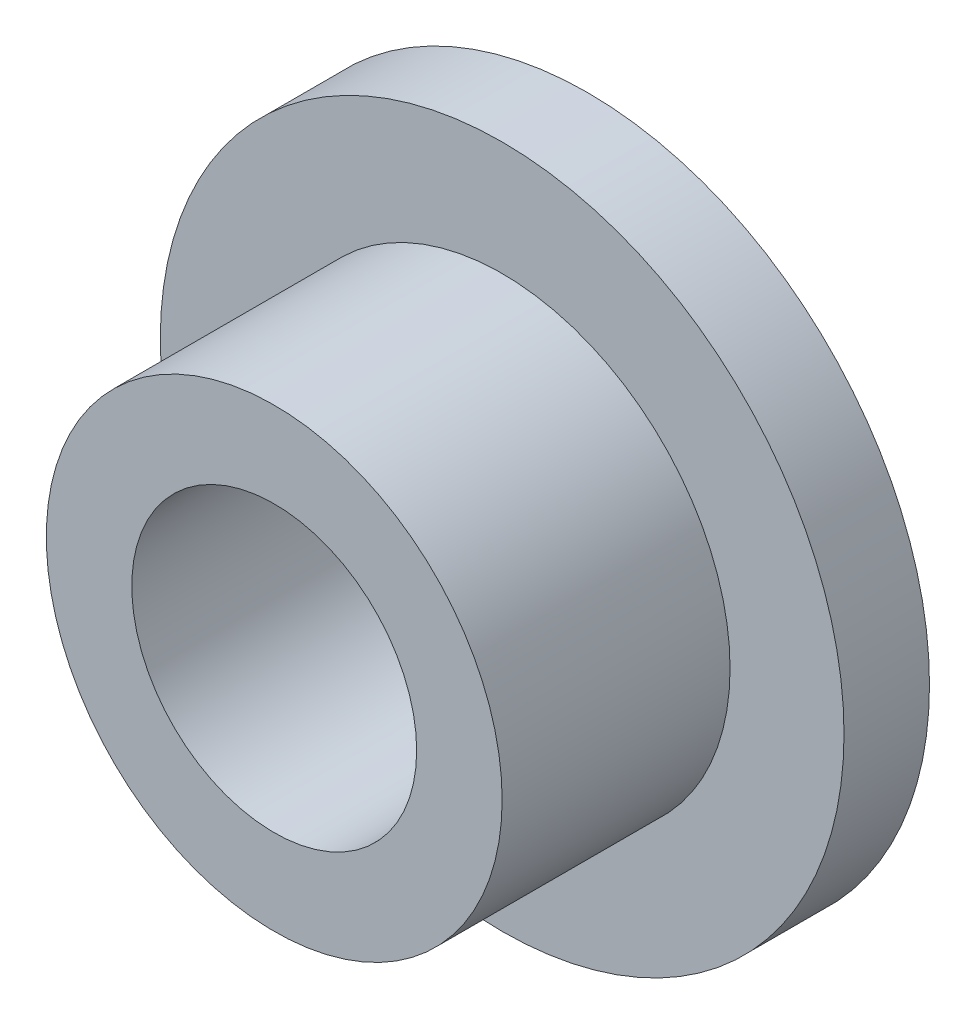
SolidWorks part; units mm, degrees
material "Aluminum Bronze"
ref_plane "Front Plane" through (0, 0, 0) normal (0, 0, 1) x (1, 0, 0)
ref_plane "Top Plane" through (0, 0, 0) normal (0, 1, 0) x (1, 0, 0)
ref_plane "Right Plane" through (0, 0, 0) normal (1, 0, 0) x (0, 0, -1)
sketch "Sketch1" plane through (0, 0, 0) normal (0, 0, 1) x (1, 0, 0)
  circle A0 centre (0, 0) radius 4
  circle A1 centre (0, 0) radius 6
  circle A2 centre (0, 0) radius 2.5
  dimension "D1" = 12
  dimension "D2" = 8
  dimension "5" = 5
extrude "Boss-Extrude1" add sketch "Sketch1" along normal blind 1.5 contours A1 A0 region at (-5.8303, 0, 0)
extrude "Boss-Extrude2" add sketch "Sketch1<3>" along normal blind 5.5 contours A0 A2 region at (-3.8869, 0, 0)
sketch "Sketch1<3>" plane through (0, 0, 0) normal (0, 0, 1) x (1, 0, 0) same geometry as "Sketch1"
